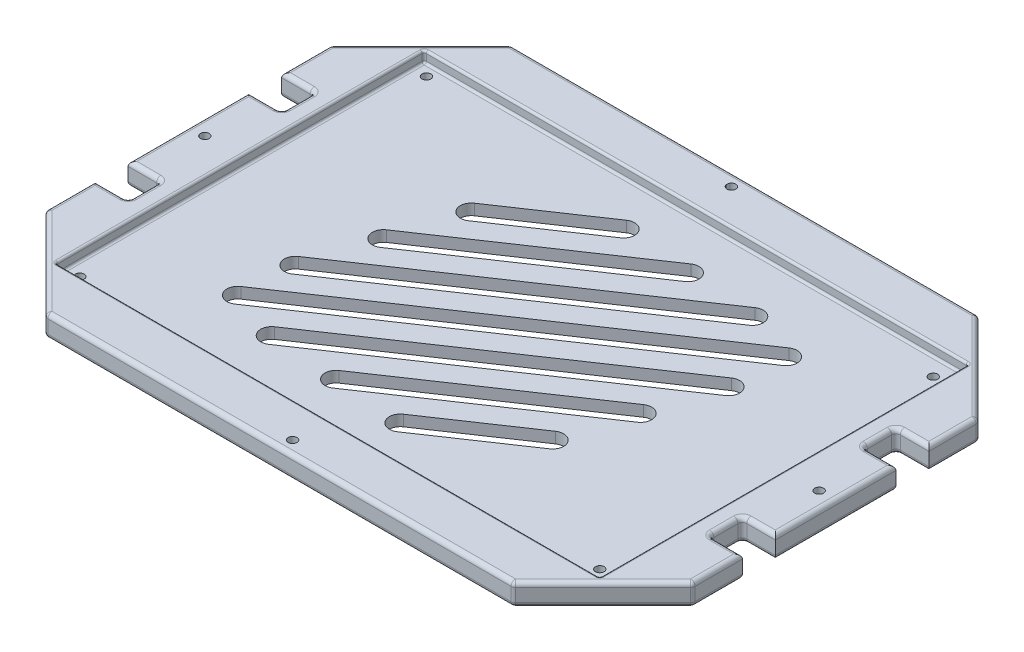
SolidWorks part; units mm, degrees
ref_plane "Front Plane" through (0, 0, 0) normal (0, 0, 1) x (1, 0, 0)
ref_plane "Top Plane" through (0, 0, 0) normal (0, 1, 0) x (1, 0, 0)
ref_plane "Right Plane" through (0, 0, 0) normal (1, 0, 0) x (0, 0, -1)
sketch "Sketch1" plane through (0, 0, 0) normal (0, 1, 0) x (1, 0, 0)
  line L0 (110.0381, -116.5) -> (156, -70.5381) construction
  line L1 (-55, 0) -> (55, 0) construction
  line L2 (-147.5, -64.8959) -> (-147.5, 64.8959)
  line L3 (-147.5, -106) -> (-106.3959, -106) construction
  line L4 (147.5, -64.8959) -> (147.5, 64.8959)
  line L5 (-147.5, -106) -> (147.5, 106) construction
  line L6 (-147.5, 106) -> (147.5, -106) construction
  line L7 (-110.0381, -116.5) -> (110.0381, -116.5) construction
  line L8 (-156, -70.5381) -> (-156, 70.5381) construction
  line L9 (-110.0381, 116.5) -> (110.0381, 116.5) construction
  line L10 (156, -70.5381) -> (156, 70.5381) construction
  line L11 (-156, -116.5) -> (156, 116.5) construction
  line L12 (-156, 116.5) -> (156, -116.5) construction
  line L14 (110.0381, -116.5) -> (156, -116.5) construction
  line L15 (156, -116.5) -> (156, -70.5381) construction
  line L16 (147.5, -106) -> (147.5, -64.8959) construction
  line L17 (106.3959, 106) -> (147.5, 64.8959)
  line L18 (110.0381, 116.5) -> (156, 70.5381) construction
  line L20 (106.3959, -106) -> (147.5, -106) construction
  line L21 (106.3959, -106) -> (147.5, -64.8959)
  line L22 (106.3959, 106) -> (147.5, 106) construction
  line L29 (110.0381, 116.5) -> (156, 116.5) construction
  line L30 (156, 70.5381) -> (156, 116.5) construction
  line L31 (147.5, 106) -> (147.5, 64.8959) construction
  line L32 (0, -55) -> (0, 55) construction
  line L33 (-110.0381, -116.5) -> (-156, -70.5381) construction
  line L34 (-106.3959, -106) -> (-147.5, -64.8959)
  line L35 (-110.0381, 116.5) -> (-156, 70.5381) construction
  line L36 (-156, 116.5) -> (-110.0381, 116.5) construction
  line L37 (-156, 70.5381) -> (-156, 116.5) construction
  line L38 (-147.5, 64.8959) -> (-147.5, 106) construction
  line L39 (-106.3959, 106) -> (-147.5, 64.8959)
  line L40 (-106.3959, 106) -> (106.3959, 106)
  line L41 (-147.5, 106) -> (-106.3959, 106) construction
  line L43 (-147.5, -106) -> (-147.5, -64.8959) construction
  line L45 (-106.3959, -106) -> (106.3959, -106)
  line L48 (-156, -116.5) -> (-156, -70.5381) construction
  line L49 (-156, -116.5) -> (-110.0381, -116.5) construction
  line L51 (102.967, -109.4289) -> (148.9289, -63.467) construction
  point P0 (0, 0)
  point P5 (0, 0)
  dimension "D1" = 295
  dimension "D2" = 212
  dimension "D3" = 233
  dimension "D4" = 312
  dimension "D5" = 65
  dimension "D6" = 45
  dimension "D7" = 10
extrude "Boss-Extrude1" add sketch "Sketch1" along normal mid plane 10 contours L34 L45 L21 L4 L17 L40 L39 L2 | L9 L35 L8 L33 L7 L0 L10 L18 L45 L34 L2 L39 L40 L17 L4 L21 region at (0, 0, 0)
sketch "Sketch4" plane through (0, 5, 0) normal (0, 1, 0) x (1, 0, 0)
  line L0 (-55, 0) -> (55, 0) construction
  line L1 (-124, -84) -> (124, -84)
  line L2 (-124, -84) -> (-124, 84)
  line L3 (-124, 84) -> (124, 84)
  line L4 (124, -84) -> (124, 84)
  line L5 (-124, -84) -> (124, 84) construction
  line L6 (-124, 84) -> (124, -84) construction
  line L7 (-123, -82) -> (123, -82) construction
  line L8 (-123, -82) -> (-123, 82) construction
  line L9 (-123, 82) -> (123, 82) construction
  line L10 (123, -82) -> (123, 82) construction
  line L11 (-123, -82) -> (123, 82) construction
  line L12 (-123, 82) -> (123, -82) construction
  circle A0 centre (-118, 79) radius 2
  circle A1 centre (-118, -79) radius 2
  circle A2 centre (116, 76) radius 2
  circle A3 centre (116, -76) radius 2
  point P0 (0, 0)
  point P6 (0, 0)
  dimension "D5" = 5
  dimension "D7" = 4
  dimension "D8" = 4
  dimension "D9" = 4
  dimension "D1" = 168
  dimension "D2" = 248
  dimension "D3" = 164
  dimension "D4" = 246
  dimension "D6" = 5
  dimension "D10" = 7
  dimension "D11" = 6
  dimension "D12" = 6
extrude "Cut-Extrude2" cut sketch "Sketch4" against normal blind 5 contours L1 L4 L3 L2 A3 A2 A0 A1 | A0 | A2 | A3 | A1 region at (0.0012, 5, 0) region at (-118, 5, -79) region at (-118, 5, 79) region at (116, 5, -76) region at (116, 5, 76)
sketch "Sketch5" plane through (0, 5, 0) normal (0, 1, 0) x (1, 0, 0)
  line L0 (-147.5, -64.8959) -> (-147.5, 64.8959) construction
  line L1 (-106.3959, 106) -> (106.3959, 106) construction
  line L2 (-106.3959, -106) -> (106.3959, -106) construction
  line L3 (147.5, -64.8959) -> (147.5, 64.8959) construction
  line L4 (0, -5.5) -> (0, 5.5) construction
  line L5 (-147.5, 42.5) -> (-132.5, 42.5)
  line L6 (-147.5, 42.5) -> (-147.5, 27.5)
  line L7 (-147.5, 27.5) -> (-132.5, 27.5)
  line L8 (-132.5, 42.5) -> (-132.5, 27.5)
  line L9 (-147.5, 42.5) -> (-132.5, 27.5) construction
  line L10 (-147.5, 27.5) -> (-132.5, 42.5) construction
  line L11 (-147.5, -27.5) -> (-132.5, -27.5)
  line L12 (-147.5, -27.5) -> (-147.5, -42.5)
  line L13 (-147.5, -42.5) -> (-132.5, -42.5)
  line L14 (-132.5, -27.5) -> (-132.5, -42.5)
  line L15 (-147.5, -27.5) -> (-132.5, -42.5) construction
  line L16 (-147.5, -42.5) -> (-132.5, -27.5) construction
  line L17 (147.5, -42.5) -> (132.5, -27.5) construction
  line L18 (147.5, -27.5) -> (132.5, -42.5) construction
  line L19 (147.5, 27.5) -> (132.5, 42.5) construction
  line L20 (147.5, 42.5) -> (132.5, 27.5) construction
  line L21 (132.5, -27.5) -> (132.5, -42.5) construction
  line L22 (147.5, -42.5) -> (132.5, -42.5) construction
  line L23 (147.5, -27.5) -> (147.5, -42.5) construction
  line L24 (147.5, -27.5) -> (132.5, -27.5) construction
  line L25 (132.5, 42.5) -> (132.5, 27.5) construction
  line L26 (147.5, 27.5) -> (132.5, 27.5) construction
  line L27 (147.5, 42.5) -> (147.5, 27.5) construction
  line L28 (147.5, 42.5) -> (132.5, 42.5) construction
  circle A0 centre (-140, 0) radius 2
  circle A1 centre (140, 0) radius 2 construction
  circle A2 centre (0, 100) radius 2
  circle A3 centre (0, -100) radius 2
  circle A4 centre (140, 0) radius 2 construction
  point P22 (-140, -35)
  point P26 (-140, 35)
  point P38 (140, 35)
  point P39 (140, -35)
  dimension "D1" = 4
  dimension "D4" = 4
  dimension "D2" = 7.5
  dimension "D3" = 6
  dimension "D5" = 6
  dimension "D6" = 7.5
  dimension "D7" = 15
  dimension "D8" = 15
  dimension "D9" = 35
  dimension "D10" = 35
  dimension "D11" = 15
  dimension "D12" = 15
extrude "Cut-Extrude3" cut sketch "Sketch5" against normal through all both and the other way through all
mirror "Mirror1" about plane through (0, 0, 0) normal (1, 0, 0) of "Cut-Extrude3"
extrude "Cut-Extrude4" cut sketch "Sketch4<3>" against normal through all both contours A1 | A2 | A3 | A0 region at (-118, 5, 79) region at (116, 5, -76) region at (116, 5, 76)
sketch "Sketch4<3>" plane through (0, 5, 0) normal (0, 1, 0) x (1, 0, 0) same geometry as "Sketch4"
fillet "Fillet1" radius 2 64 edges at (140, 5, 42.5) (140, 5, 27.5) (140, -5, 27.5) (140, -5, 42.5) (140, 5, -27.5) (140, 5, -42.5) (140, -5, -42.5) (140, -5, -27.5) (-140, -5, 42.5) (-140, 5, 42.5) (-140, -5, 27.5) (-140, 5, 27.5) (-140, -5, -27.5) (-140, 5, -27.5) (-140, -5, -42.5) (-140, 5, -42.5) (132.5, 5, 35) (132.5, 0, 27.5) (132.5, -5, 35) (132.5, 0, 42.5) (132.5, 5, -35) (132.5, 0, -42.5) (132.5, -5, -35) (132.5, 0, -27.5) (-132.5, 0, 42.5) (-132.5, -5, 35) (-132.5, 0, 27.5) (-132.5, 5, 35) (-132.5, 0, -27.5) (-132.5, -5, -35) (-132.5, 0, -42.5) (-132.5, 5, -35) (-126.948, -5, 85.448) (0, -5, 106) (126.948, -5, 85.448) (147.5, -5, -53.698) (147.5, -5, 0) (147.5, -5, 53.698) (126.948, -5, -85.448) (0, -5, -106) (-126.948, -5, -85.448) (-147.5, -5, -53.698) (-147.5, -5, 0) (-147.5, -5, 53.698) (-126.948, 5, 85.448) (0, 5, 106) (126.948, 5, 85.448) (147.5, 5, -53.698) (147.5, 5, 0) (147.5, 5, 53.698) (126.948, 5, -85.448) (0, 5, -106) (-126.948, 5, -85.448) (-147.5, 5, -53.698) (-147.5, 5, 0) (-147.5, 5, 53.698) (-147.5, 0, 64.8959) (-147.5, 0, -64.8959) (-106.3959, 0, -106) (106.3959, 0, -106) (147.5, 0, -64.8959) (-106.3959, 0, 106) (147.5, 0, 64.8959) (106.3959, 0, 106)
fillet "Fillet2" radius 1 12 edges at (0, 0, 84) (124, 0, 0) (0, 0, -84) (-124, 0, 0) (-124, 2.5, 84) (124, 2.5, 84) (0, 5, 84) (124, 2.5, -84) (-124, 2.5, -84) (124, 5, 0) (0, 5, -84) (-124, 5, 0)
sketch "Sketch6" plane through (0, 0, 0) normal (0, 1, 0) x (1, 0, 0)
  line L0 (-123, 0) -> (123, 0) construction
  line L1 (-123, 83) -> (-123, -83) construction
  line L2 (123, -83) -> (123, 83) construction
  line L3 (0, 83) -> (0, -84) construction
  line L4 (123, 83) -> (-123, 83) construction
  line L5 (123, -84) -> (-123, -84) construction
  line L6 (-108, 30) -> (-108, -30)
  line L7 (-108, -30) -> (-78, -30)
  line L8 (-78, -30) -> (-67.4204, 30)
  line L9 (-67.4204, 30) -> (-42.4204, 30)
  line L10 (-42.4204, 30) -> (-31.8408, -30)
  line L11 (-31.8408, -30) -> (-21.8408, -30)
  line L12 (-21.8408, -30) -> (-21.8408, 30)
  line L13 (-21.8408, 30) -> (-11.8408, 30)
  line L14 (-1.8408, 0) -> (8.1592, 0)
  line L15 (-11.8408, 30) -> (-1.8408, 0)
  line L16 (18.1592, 30) -> (8.1592, 0)
  line L17 (18.1592, 30) -> (28.1592, 30)
  line L18 (28.1592, 30) -> (28.1592, -30)
  line L20 (28.1592, -30) -> (38.1592, -30)
  line L21 (38.1592, -30) -> (38.1592, 30)
  line L22 (38.1592, 30) -> (68.1592, 30)
  line L23 (68.1592, 30) -> (68.1592, 0)
  line L24 (68.1592, 0) -> (58.1592, 0)
  line L25 (58.1592, 0) -> (63.1592, -30)
  line L26 (63.1592, -30) -> (108, -30)
  line L27 (108, -30) -> (108, -20)
  line L28 (108, -20) -> (78.1592, -20)
  line L29 (78.1592, -20) -> (78.1592, 30)
  line L30 (78.1592, 30) -> (108, 30)
  line L31 (-113, 30) -> (-113, -35)
  line L32 (-113, -35) -> (-73.8045, -35)
  line L33 (-73.8045, -35) -> (-63.2249, 25)
  line L34 (-63.2249, 25) -> (-46.6159, 25)
  line L35 (-46.6159, 25) -> (-36.0363, -35)
  line L36 (-36.0363, -35) -> (-16.8408, -35)
  line L37 (-16.8408, -35) -> (-16.8408, 25)
  line L38 (-16.8408, 25) -> (-15.4446, 25)
  line L39 (-15.4446, 25) -> (-5.4446, -5)
  line L40 (-5.4446, -5) -> (11.763, -5)
  line L41 (21.763, 25) -> (11.763, -5)
  line L42 (21.763, 25) -> (23.1592, 25)
  line L43 (23.1592, 25) -> (23.1592, -35)
  line L44 (23.1592, -35) -> (43.1592, -35)
  line L45 (43.1592, -35) -> (43.1592, 25)
  line L46 (43.1592, 25) -> (63.1592, 25)
  line L47 (63.1592, 25) -> (63.1592, 5)
  line L48 (63.1592, 5) -> (52.2569, 5)
  line L49 (52.2569, 5) -> (58.9236, -35)
  line L50 (58.9236, -35) -> (113, -35)
  line L51 (113, -35) -> (113, -15)
  line L52 (113, -15) -> (83.1592, -15)
  line L53 (83.1592, -15) -> (83.1592, 25)
  line L54 (83.1592, 25) -> (108, 25)
  line L55 (-113, 30) -> (-108, 30)
  line L56 (108, 30) -> (108, 25)
  line L57 (-70, 45) -> (70, 45) construction
  line L58 (-37.5, -70) -> (37.5, -70) construction
  text T0 "T-WORKS" font "Times New Roman" height 20
  text T1 "2025" font "Times New Roman" height 20
  point P14 (3.1592, 0)
  point P65 (0, 45)
  point P69 (0, -70)
  dimension "D1" = 60
  dimension "D2" = 30
  dimension "D3" = 100
  dimension "D4" = 100
  dimension "D5" = 15
  dimension "D6" = 30
  dimension "D7" = 25
  dimension "D8" = 10
  dimension "D9" = 50
  dimension "D10" = 10
  dimension "D11" = 25
  dimension "D12" = 10
  dimension "D13" = 10
  dimension "D14" = 30
  dimension "D15" = 10
  dimension "D16" = 30
  dimension "D17" = 25
  dimension "D18" = 10
  dimension "D19" = 15
  dimension "D20" = 10
  dimension "D22" = 45
  dimension "D23" = 140
  dimension "D24" = 35
  dimension "D25" = 75
  dimension "D21" = 5
extrude "Cut-Extrude5" [suppressed] cut sketch "Sketch6" against normal through all both and the other way through all
sketch "Sketch7" plane through (0, 0, 0) normal (0, 1, 0) x (1, 0, 0)
  line L0 (-123, -83) -> (123, 83) construction
  line L1 (123, -83) -> (123, 83) construction
  line L2 (-74.6034, -50.3421) -> (74.6034, 50.3421) construction
  line L3 (-77.4002, -46.1975) -> (71.8066, 54.4868)
  line L4 (-71.8066, -54.4868) -> (77.4002, 46.1975)
  line L5 (0, 0) -> (-41.3041, 61.2097) construction
  line L6 (0, 0) -> (37.8874, -56.1464) construction
  line L7 (-73.3567, -25.3732) -> (50.9824, 58.5303) construction
  line L8 (-76.1534, -21.2286) -> (48.1856, 62.675)
  line L9 (-70.5599, -29.5179) -> (53.7792, 54.3857)
  line L10 (-63.8206, 5.1892) -> (19.0721, 61.1249) construction
  line L11 (-66.6174, 9.3339) -> (16.2753, 65.2696)
  line L12 (-61.0238, 1.0446) -> (21.8688, 56.9803)
  line L13 (-54.2846, 35.7517) -> (-12.8383, 63.7195) construction
  line L14 (-57.0814, 39.8963) -> (-15.635, 67.8642)
  line L15 (-51.4878, 31.607) -> (-10.0415, 59.5749)
  line L16 (-50.9824, -58.5303) -> (73.3567, 25.3732) construction
  line L17 (-48.1856, -62.675) -> (76.1534, 21.2286)
  line L18 (-53.7792, -54.3857) -> (70.5599, 29.5179)
  line L19 (-19.0721, -61.1249) -> (63.8206, -5.1892) construction
  line L20 (-16.2753, -65.2696) -> (66.6174, -9.3339)
  line L21 (-21.8688, -56.9803) -> (61.0238, -1.0446)
  line L22 (12.8383, -63.7195) -> (54.2846, -35.7517) construction
  line L23 (15.635, -67.8642) -> (57.0814, -39.8963)
  line L24 (10.0415, -59.5749) -> (51.4878, -31.607)
  arc A0 (-76.1534, -21.2286) -> (-70.5599, -29.5179) centre (-73.3567, -25.3732) ccw
  arc A1 (-77.4002, -46.1975) -> (-71.8066, -54.4868) centre (-74.6034, -50.3421) ccw
  arc A2 (77.4002, 46.1975) -> (71.8066, 54.4868) centre (74.6034, 50.3421) ccw
  arc A3 (53.7792, 54.3857) -> (48.1856, 62.675) centre (50.9824, 58.5303) ccw
  arc A4 (-66.6174, 9.3339) -> (-61.0238, 1.0446) centre (-63.8206, 5.1892) ccw
  arc A5 (21.8688, 56.9803) -> (16.2753, 65.2696) centre (19.0721, 61.1249) ccw
  arc A6 (-57.0814, 39.8963) -> (-51.4878, 31.607) centre (-54.2846, 35.7517) ccw
  arc A7 (-10.0415, 59.5749) -> (-15.635, 67.8642) centre (-12.8383, 63.7195) ccw
  arc A8 (-48.1856, -62.675) -> (-53.7792, -54.3857) centre (-50.9824, -58.5303) cw
  arc A9 (70.5599, 29.5179) -> (76.1534, 21.2286) centre (73.3567, 25.3732) cw
  arc A10 (-16.2753, -65.2696) -> (-21.8688, -56.9803) centre (-19.0721, -61.1249) cw
  arc A11 (61.0238, -1.0446) -> (66.6174, -9.3339) centre (63.8206, -5.1892) cw
  arc A12 (15.635, -67.8642) -> (10.0415, -59.5749) centre (12.8383, -63.7195) cw
  arc A13 (51.4878, -31.607) -> (57.0814, -39.8963) centre (54.2846, -35.7517) cw
  point P2 (0, 0)
  point P18 (-11.1871, 16.5785)
  point P23 (-22.3743, 33.1571)
  point P30 (-33.5614, 49.7356)
  point P40 (11.1871, -16.5785)
  point P47 (22.3743, -33.1571)
  point P54 (33.5614, -49.7356)
  dimension "D1" = 180
  dimension "D2" = 10
  dimension "D3" = 90
  dimension "D4" = 10
  dimension "D5" = 150
  dimension "D6" = 100
  dimension "D7" = 20
  dimension "D8" = 20
  dimension "D9" = 20
  dimension "D10" = 10
  dimension "D11" = 10
  dimension "D12" = 50
extrude "Cut-Extrude6" cut sketch "Sketch7" against normal through all both and the other way through all
